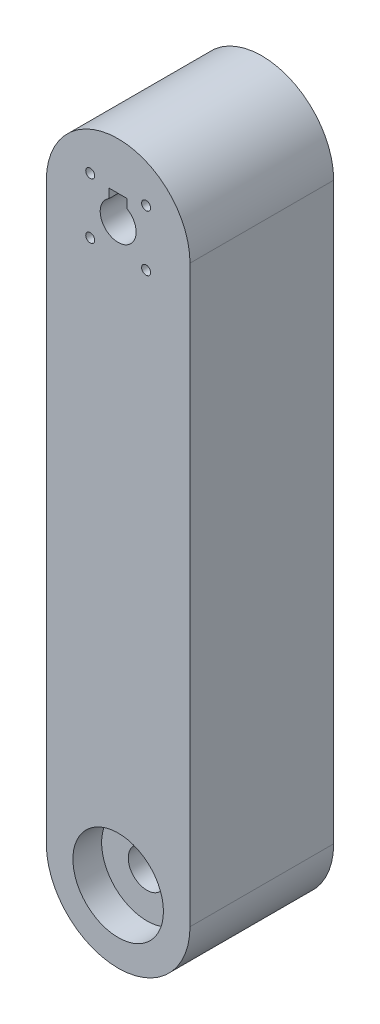
SolidWorks part; units mm, degrees
material "ABS"
ref_plane "Front Plane" through (0, 0, 0) normal (0, 0, 1) x (1, 0, 0)
ref_plane "Top Plane" through (0, 0, 0) normal (0, 1, 0) x (1, 0, 0)
ref_plane "Right Plane" through (0, 0, 0) normal (1, 0, 0) x (0, 0, -1)
sketch "Sketch1" plane through (0, 0, 0) normal (0, 0, 1) x (1, 0, 0)
  line L2 (12.7, 50.8) -> (12.7, -50.8)
  line L4 (-12.7, 50.8) -> (-12.7, -50.8)
  line L5 (12.7, 50.8) -> (-12.7, -50.8) construction
  line L6 (12.7, -50.8) -> (-12.7, 50.8) construction
  arc A0 (-12.7, 50.8) -> (12.7, 50.8) centre (0, 50.8) cw
  arc A1 (-12.7, -50.8) -> (12.7, -50.8) centre (0, -50.8) ccw
  point P0 (0, 0)
  dimension "D1" = 101.6
  dimension "D2" = 25.4
extrude "Boss-Extrude1" add sketch "Sketch1" along normal blind 25.4
sketch "Sketch2" plane through (0, 0, 25.4) normal (0, 0, 1) x (1, 0, 0)
  line L0 (-4.9391, 55.7391) -> (4.9391, 45.8609) construction
  line L1 (4.9391, 55.7391) -> (-4.9391, 45.8609) construction
  line L2 (0, 50.8) -> (0, 59.0413) construction
  circle A0 centre (0, 50.8) radius 3.175
  circle A1 centre (-4.9391, 55.7391) radius 0.7938
  circle A2 centre (-4.9391, 45.8609) radius 0.7937
  circle A3 centre (4.9391, 55.7391) radius 0.7938
  circle A4 centre (4.9391, 45.8609) radius 0.7938
  point P8 (0, 50.8)
  point P9 (0, 50.8)
  dimension "D1" = 6.35
  dimension "D4" = 1.5875
  dimension "D2" = 45
  dimension "D3" = 13.97
extrude "Cut-Extrude1" cut sketch "Sketch2" against normal up to next
sketch "Sketch3" plane through (0, 0, 25.4) normal (0, 0, 1) x (1, 0, 0)
  line L1 (-1.5875, 55.1371) -> (1.5875, 55.1371)
  line L2 (-1.5875, 55.1371) -> (-1.5875, 53.5496)
  line L3 (-1.5875, 53.5496) -> (1.5875, 53.5496)
  line L4 (1.5875, 55.1371) -> (1.5875, 53.5496)
  circle A0 centre (0, 50.8) radius 3.175 construction
  dimension "D1" = 3.175
  dimension "D2" = 1.5875
extrude "Cut-Extrude2" cut sketch "Sketch3" against normal through all
sketch "Sketch4" plane through (0, 0, 25.4) normal (0, 0, 1) x (1, 0, 0)
  circle A0 centre (0, -50.8) radius 8.001
  dimension "D1" = 16.002
extrude "Cut-Extrude3" cut sketch "Sketch4" against normal blind 5.08
ref_plane "Plane1" through (0, 0, 12.7) normal (0, 0, 1) x (1, 0, 0)
mirror "Mirror1" about plane through (0, 0, 12.7) normal (0, 0, 1) of "Cut-Extrude3"
sketch "Sketch5" plane through (0, 0, 20.32) normal (0, 0, 1) x (1, 0, 0)
  circle A0 centre (0, -50.8) radius 3.302
  circle A1 centre (0, -50.8) radius 8.001 construction
  dimension "D1" = 6.604
extrude "Cut-Extrude4" cut sketch "Sketch5" against normal through all
ref_axis "Axis1" through (0, 50.8, 0) along (0, 0, 1)
ref_plane "Plane2" through (0, 0, 12.7) normal (0, 0, 1) x (1, 0, 0)
ref_point "Point1"
ref_plane "Plane3" through (0, 0, -16.31) normal (0, 0, 1) x (1, 0, 0)
ref_axis "Axis2" through (0, -50.8, 5.08) along (0, 0, 1)
ref_point "Leg frame 2 orgin"
